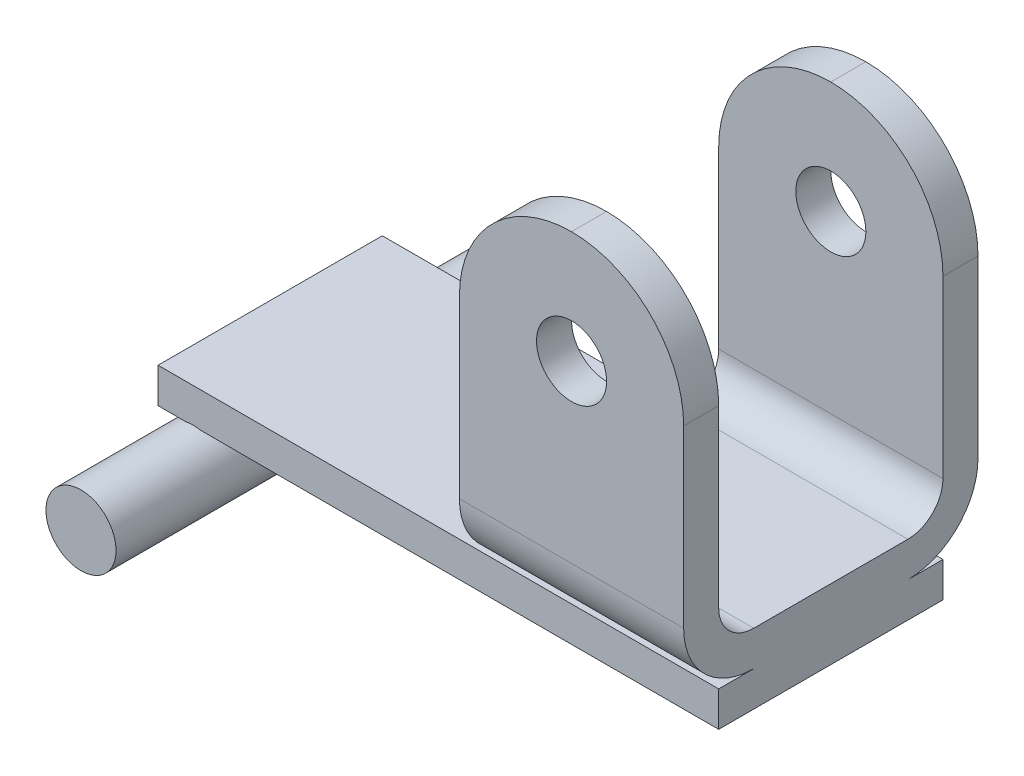
SolidWorks part; units mm, degrees
ref_plane "Plan1" through (0, 0, 0) normal (0, 0, 1) x (1, 0, 0)
ref_plane "Plan2" through (0, 0, 0) normal (0, 1, 0) x (1, 0, 0)
ref_plane "Plan3" through (0, 0, 0) normal (1, 0, 0) x (0, 0, -1)
sketch "Esquisse1" plane through (0, 0, 0) normal (0, 0, 1) x (1, 0, 0)
  circle A0 centre (0, 0) radius 0.5
  dimension "D1" = 1
extrude "Base-Extrusion" add sketch "Esquisse1" along normal mid plane 6.4
sketch "Esquisse2" plane through (0, 0, 0) normal (0, 0, 1) x (1, 0, 0)
  line L1 (-0.5, 0.99) -> (7.5, 0.99)
  line L2 (-0.5, 0.99) -> (-0.5, 0.49)
  line L3 (-0.5, 0.49) -> (7.5, 0.49)
  line L4 (7.5, 0.99) -> (7.5, 0.49)
  dimension "D1" = 0.5
  dimension "D2" = 0.5
  dimension "D3" = 8
  dimension "D4" = 0.49
extrude "Boss.-Extru.3" add sketch "Esquisse2" along normal mid plane 3.2
sketch "Esquisse3" plane through (7.5, 0, 0) normal (1, 0, 0) x (0, 0, -1)
  line L3 (-2.1, 6.09) -> (-2.1, 1.99)
  line L5 (-1.1, 0.99) -> (1.1, 0.99)
  line L6 (2.1, 6.09) -> (2.1, 1.99)
  arc A0 (-1.1, 0.99) -> (-2.1, 1.99) centre (-1.1, 1.99) cw
  arc A1 (2.1, 1.99) -> (1.1, 0.99) centre (1.1, 1.99) cw
  point P6 (-2.1, 0.99)
  point P9 (2.1, 0.99)
  dimension "D2" = 4.2
  dimension "D5" = 1
  dimension "D1" = 2.1
  dimension "D3" = 5.1
  dimension "D4" = 0.99
extrude "Boss.-Extru.-Mince1" add sketch "Esquisse3" against normal blind 3.2 thin
sketch "Esquisse4" plane through (0, 0, 2.1) normal (0, 0, 1) x (1, 0, 0)
  line L0 (7.5, 1.99) -> (7.5, 6.09) construction
  line L1 (7.5, 0.99) -> (-0.5, 0.99) construction
  circle A0 centre (5.9, 4.49) radius 0.5
  dimension "D1" = 1
  dimension "D2" = 1.6
  dimension "D3" = 3.5
extrude "Enlèv. mat.-Extru.1" cut sketch "Esquisse4" against normal through all
fillet "Congé1" radius 1.6
